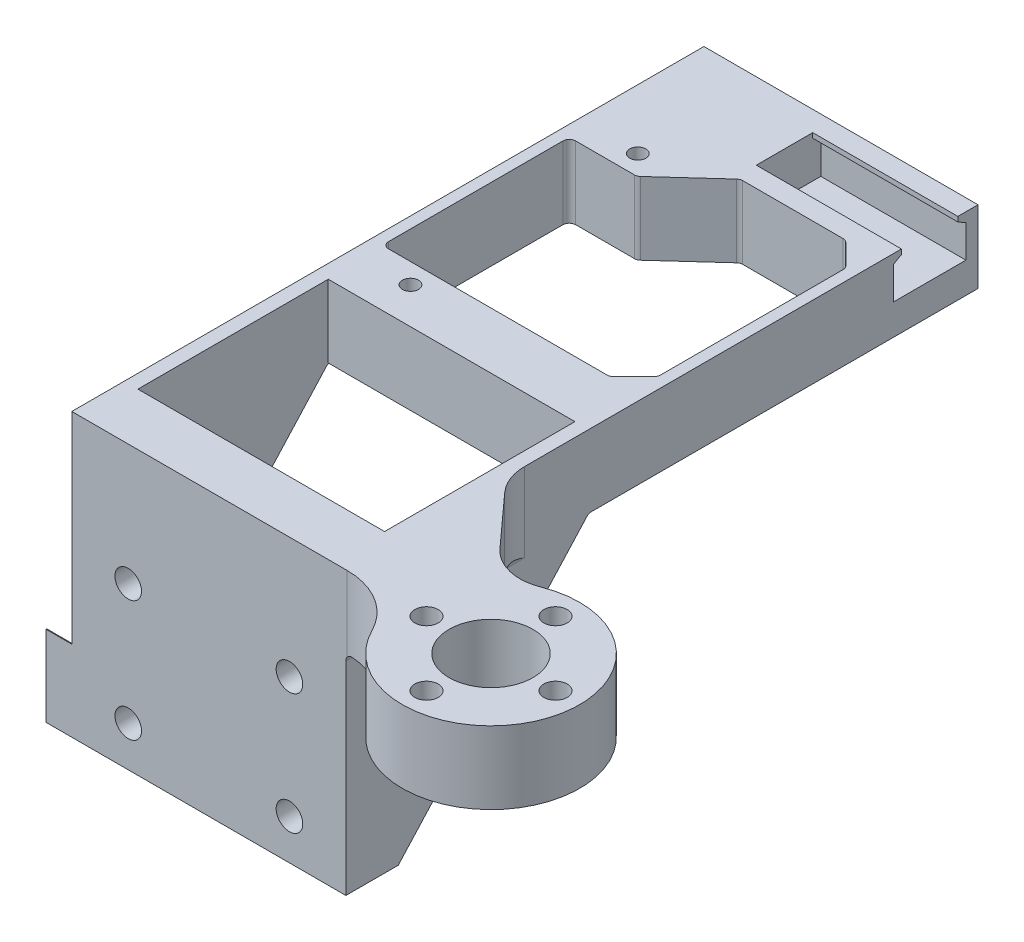
SolidWorks part; units mm, degrees
ref_plane "Front Plane" through (0, 0, 0) normal (0, 0, 1) x (1, 0, 0)
ref_plane "Top Plane" through (0, 0, 0) normal (0, 1, 0) x (1, 0, 0)
ref_plane "Right Plane" through (0, 0, 0) normal (1, 0, 0) x (0, 0, -1)
sketch "Sketch1" plane through (0, 0, 0) normal (0, 1, 0) x (1, 0, 0)
  line L0 (0, 0) -> (0, 59.6401) construction
  line L1 (-20, -19.2885) -> (-21.4, -19.2885)
  line L2 (20, 17.7115) -> (21.4, 17.7115)
  line L3 (20, 17.7115) -> (20, 69.9115)
  line L4 (20, 69.9115) -> (21.4, 69.9115)
  line L5 (21.4, 17.7115) -> (21.4, 69.9115)
  line L6 (20, 17.7115) -> (21.4, 17.7115)
  line L7 (20, 17.7115) -> (20, -19.2885)
  line L8 (20, -19.2885) -> (21.4, -19.2885)
  line L9 (21.4, 17.7115) -> (21.4, -19.2885)
  line L10 (-21.4, 17.7115) -> (-21.4, -19.2885)
  line L11 (-20, 17.7115) -> (-21.4, 17.7115)
  line L12 (-20, 17.7115) -> (-20, -19.2885)
  line L13 (-20, 69.9115) -> (-21.4, 69.9115)
  line L14 (-21.4, 17.7115) -> (-21.4, 69.9115)
  line L15 (-20, 17.7115) -> (-21.4, 17.7115)
  line L16 (-20, 17.7115) -> (-20, 69.9115)
  dimension "18" = 20
  dimension "D2" = 1.4
  dimension "D3" = 37
  dimension "D4" = 52.2
extrude "Boss-Extrude1" add sketch "Sketch1" against normal blind 9 from offset 1 contours L12 L11 L10 L1 | L11 L16 L13 L14 | L3 L2 L5 L4 offset against normal yes
sketch "Sketch4" plane through (0, -10, 0) normal (0, -1, 0) x (1, 0, 0)
  line L0 (-21.4, -69.9115) -> (-21.4, 19.2885) construction
  line L1 (12, -69.9115) -> (-21.4, -69.9115)
  line L2 (12, -69.9115) -> (12, -57.9115)
  line L3 (12, -57.9115) -> (-21.4, -57.9115)
  line L4 (-21.4, -69.9115) -> (-21.4, -57.9115)
  line L10 (-20, -69.9115) -> (-20, 19.2885) construction
  line L13 (-20, -69.9115) -> (-21.4, -69.9115) construction
  dimension "D1" = 12
  dimension "D2" = 32
extrude "Boss-Extrude3" add sketch "Sketch4" against normal up to surface (9 mm away) up to face at (-20.7, -1, -25.3115)
sketch "Sketch3" plane through (0, -10, 0) normal (0, -1, 0) x (1, 0, 0)
  line L0 (-21.4, -69.9115) -> (-21.4, 19.2885) construction
  line L1 (-21.4, -58.8115) -> (-7.4, -58.8115)
  line L2 (-21.4, -58.8115) -> (-21.4, -51.8115)
  line L3 (-21.4, -51.8115) -> (-7.4, -51.8115)
  line L4 (-7.4, -58.8115) -> (-7.4, -51.8115)
  line L6 (0, 0) -> (0, -31.4212) construction
  line L13 (12, -69.9115) -> (-21.4, -69.9115) construction
  line L14 (-21.4, -40.2115) -> (-3.8096, -40.2115) construction
  line L15 (-21.4, -28.6115) -> (-7.4, -28.6115)
  line L16 (-7.4, -21.6115) -> (-7.4, -28.6115)
  line L17 (-21.4, -21.6115) -> (-7.4, -21.6115)
  line L18 (-21.4, -21.6115) -> (-21.4, -28.6115)
  line L19 (-20, -57.9115) -> (-20, 19.2885) construction
  circle A0 centre (-14, -54.3115) radius 1
  circle A2 centre (-14, -26.1115) radius 1
  dimension "D4" = 2.5
  dimension "D5" = 2
  dimension "D1" = 14.1
  dimension "D2" = 15.6
  dimension "D3" = 7
  dimension "D6" = 6
  dimension "D7" = 14
extrude "Servo Holder" add sketch "Sketch3" along normal blind 1 and the other way offset from surface (9 mm away) 1 other way up to plane "Top Plane"
sketch "Sketch37" plane through (0, -1, 0) normal (0, 1, 0) x (1, 0, 0)
  line L0 (-7.4, 21.6115) -> (-20, 21.6115) construction
  line L1 (12.6, 21.6115) -> (-7.4, 21.6115)
  line L2 (12.6, 21.6115) -> (12.6, 28.6115)
  line L3 (12.6, 28.6115) -> (-7.4, 28.6115)
  line L4 (-7.4, 21.6115) -> (-7.4, 28.6115)
  line L5 (-21.4, 69.9115) -> (-21.4, -19.2885) construction
  dimension "D1" = 34
extrude "Boss-Extrude19" add sketch "Sketch37" against normal up to surface (10 mm away) up to face at (-14.4, -11, -25.1115)
sketch "Sketch29" plane through (0, 0, -69.9115) normal (0, 0, -1) x (-1, 0, 0)
  line L1 (21.4, -10) -> (-12.7099, -10)
  line L2 (21.4, -10) -> (21.4, -16.1774)
  line L3 (21.4, -16.1774) -> (-12.7099, -16.1774)
  line L4 (-12.7099, -10) -> (-12.7099, -16.1774)
extrude "Cut-Extrude10" cut sketch "Sketch29" against normal through all both and the other way through all
sketch "Sketch30" plane through (0, 0, 0) normal (0, 0, 1) x (1, 0, 0)
  line L0 (-4.4, -1) -> (-4.4, -36) construction
  line L1 (12.6, -1) -> (-21.4, -1)
  line L2 (12.6, -1) -> (12.6, -36)
  line L3 (12.6, -36) -> (-21.4, -36)
  line L4 (-21.4, -1) -> (-21.4, -36)
  line L7 (-21.4, -1) -> (12.6, -1) construction
  line L9 (12.6, -1) -> (-20, -1) construction
  line L11 (-21.4, -10) -> (-21.4, -1) construction
  circle A0 centre (5.6, -31) radius 1.65
  circle A1 centre (5.6, -16) radius 1.65
  circle A2 centre (-14.4, -31) radius 1.65
  circle A3 centre (-14.4, -16) radius 1.65
  dimension "D2" = 10
  dimension "D4" = 15
  dimension "D7" = 3.3
  dimension "D8" = 3.3
  dimension "D1" = 17
  dimension "D3" = 35
  dimension "D5" = 15
  dimension "D6" = 10
extrude "Carriage Interface" add sketch "Sketch30" along normal blind 6.5 from offset 2 separate body
sketch "Sketch41" plane through (-20, 0, 0) normal (1, 0, 0) x (0, 0, -1)
  line L0 (21.6115, -1) -> (-19.2885, -1) construction
  line L1 (-2, -1) -> (-19.2885, -1)
  line L2 (-2, -1) -> (-2, -10)
  line L3 (-2, -10) -> (-19.2885, -10)
  line L4 (-19.2885, -1) -> (-19.2885, -10)
  line L5 (-2, -1) -> (-2, -36) construction
extrude "Cut-Extrude14" cut sketch "Sketch41" against normal blind 15
sketch "Sketch32" plane through (0, -36, 0) normal (0, -1, 0) x (1, 0, 0)
  line L0 (-21.4, 8.5) -> (12.6, 8.5) construction
  line L1 (30.6, 8.5) -> (19.6, 8.5) construction
  line L2 (30.6, 8.5) -> (12.6, 8.5) construction
  line L4 (-21.4, 8.5) -> (12.6, 8.5) construction
  circle A0 centre (30.6, 8.5) radius 5.2
  circle A1 centre (30.6, 8.5) radius 11
  circle A2 centre (22.6, 8.5) radius 1.45
  circle A3 centre (30.6, 16.5) radius 1.45
  circle A4 centre (38.6, 8.5) radius 1.45
  circle A5 centre (30.6, 0.5) radius 1.45
  point P4 (-4.4, 8.5)
  point P18 (30.6, 8.5)
  line M1 (-21.4, 2) -> (12.6, 2)
  line M2 (12.6, 2) -> (12.6, 8.5)
  line M3 (12.6, 8.5) -> (-21.4, 8.5)
  dimension "D1" = 8
  dimension "D2" = 22
  dimension "D4" = 10.4
  dimension "D5" = 35
  dimension "D3" = 4
extrude "Boss-Extrude14" add sketch "Sketch32" along normal blind 9 from surface at -35 contours A1 A5 A4 A3 A2 A0 M1 M3 M2 starting at face at (-3.7, -1, 5.25)
sketch "Sketch34" plane through (-21.4, 0, 0) normal (-1, 0, 0) x (0, 0, 1)
  line L1 (-21.6115, -1) -> (-21.6115, -10)
  line L5 (-69.9115, -1) -> (2, -1) construction
  line L6 (-69.9115, -10) -> (2, -10) construction
  line L7 (-21.6115, -10) -> (2, -36)
  line L8 (-21.6115, -10) -> (-21.6115, -1) construction
  line L9 (2, -36) -> (8.5, -36)
  line L10 (8.5, -36) -> (8.5, -1)
  line L11 (8.5, -1) -> (-21.6115, -1)
extrude "Boss-Extrude16" add sketch "Sketch34" against normal blind 1.7
sketch "Sketch35" plane through (12.6, 0, 0) normal (1, 0, 0) x (0, 0, -1)
  line L0 (-2, -1) -> (21.6115, -1)
  line L1 (21.6115, -1) -> (21.6115, -10)
  line L3 (-8.5, -9.8) -> (-8.5, -1)
  line L4 (-8.5, -1) -> (-2, -1)
  line L5 (21.6115, -10) -> (21.6115, -1) construction
  line L6 (28.6115, -10) -> (21.6115, -10) construction
  line L8 (-8.5, -36) -> (-8.5, -1) construction
  line L9 (21.6115, -1) -> (28.6115, -1) construction
  line L10 (21.6115, -10) -> (-2, -36)
  line L11 (-2, -36) -> (-8.5, -36)
  line L12 (-8.5, -36) -> (-8.5, -9.8)
extrude "Boss-Extrude17" add sketch "Sketch35" against normal blind 1.7
sketch "Sketch36" plane through (0, -10, 0) normal (0, -1, 0) x (1, 0, 0)
  line L0 (12.6, -11.3656) -> (23.214, 0.3485)
  line L1 (12.6, 8.5) -> (20.7301, 8.5)
  line L2 (23.214, 0.3485) -> (12.6, -0.1224)
  line L3 (12.6, -0.1224) -> (12.6, -11.3656)
  line L4 (30.6, 8.5) -> (12.6, -11.3656) construction
  line L5 (12.6, 8.5) -> (12.6, 2) construction
  line L6 (20.7301, 8.5) -> (23.214, 0.3485)
  line L7 (12.6, 8.5) -> (12.6, -0.1224)
  circle A1 centre (30.6, 8.5) radius 11 construction
extrude "Boss-Extrude18" add sketch "Sketch36" against normal up to surface (9 mm away) contours L1 L7 L2 L6 | L2 L3 L0
fillet "Fillet9" [suppressed] radius 1
sketch "Sketch39" plane through (0, -1, 0) normal (0, 1, 0) x (1, 0, 0)
  line L0 (-21.4, 69.9115) -> (12, 69.9115) construction
  line L1 (12.6, 28.6115) -> (11.2, 28.6115)
  line L2 (12.6, 28.6115) -> (12.6, 69.9115)
  line L3 (12.6, 69.9115) -> (11.2, 69.9115)
  line L4 (11.2, 28.6115) -> (11.2, 69.9115)
  line L5 (-20, 28.6115) -> (12.6, 28.6115) construction
  line L6 (12.6, 11.3656) -> (12.6, 28.6115) construction
  point P7 (12.6, 49.2615)
  dimension "D1" = 1.4
extrude "Boss-Extrude20" add sketch "Sketch39" against normal up to surface (9 mm away) up to face at (-4.7667, -10, -41.9115)
sketch "Sketch40" plane through (12.6, 0, 0) normal (1, 0, 0) x (0, 0, -1)
  line L1 (60.4115, -1) -> (67.4115, -1)
  line L6 (60.4115, -2.2) -> (59.4115, -2.2)
  line L7 (59.4115, -2.2) -> (59.4115, -6.2)
  line L8 (59.4115, -6.2) -> (68.4115, -6.2)
  line L9 (63.9115, -6.2) -> (63.9115, -1)
  line L11 (68.4115, -2.2) -> (68.4115, -6.2)
  line L12 (67.4115, -2.2) -> (68.4115, -2.2)
  line L13 (67.4115, -1) -> (67.4115, -2.2)
  line L14 (69.9115, -10) -> (69.9115, -1) construction
  line L15 (60.4115, -2.2) -> (60.4115, -1)
  line L16 (11.3656, -1) -> (69.9115, -1) construction
  point P9 (59.4115, -4.2)
  dimension "D1" = 6
  dimension "D2" = 3.5
  dimension "D3" = 4.5
  dimension "D4" = 4
  dimension "D5" = 1.2
  dimension "D6" = 3.5
  dimension "D7" = 1
extrude "Brush" cut sketch "Sketch40" against normal blind 18
chamfer "Chamfer2" distance 0.6 angle 60 2 edges at (3.6, -2.2, -67.4115) (3.6, -2.2, -60.4115)
chamfer "Chamfer3" distance 3 angle 45 2 edges at (11.2, -5.5, -28.6115) (11.2, -5.5, -57.9115)
fillet "Fillet10" radius 6 2 edges at (23.214, -5.5, 0.3485) (12.6, -5.5, -11.3656)
sketch "Sketch42" plane through (0, 0, 8.5) normal (0, 0, 1) x (1, 0, 0)
  line L0 (-4.4, -36) -> (-4.4, -1) construction
  line L3 (-21.4, -36) -> (12.6, -36) construction
  line L4 (19.6, -1) -> (-21.4, -1) construction
  line L5 (-0.8, -1) -> (-0.8, -10.6)
  line L6 (-8, -1) -> (-8, -10.6)
  line L7 (-0.8, -1) -> (-8, -1)
  arc A0 (-0.8, -10.6) -> (-8, -10.6) centre (-4.4, -10.6) cw
  point P11 (-4.4, -14.2)
  dimension "D1" = 3.6
  dimension "D2" = 13.2
extrude "Cut-Extrude15" [suppressed] cut sketch "Sketch42" against normal blind 10
chamfer "Chamfer4" distance 2.5 angle 45 1 edges at (-7.4, -5.5, -57.9115)
sketch "Sketch43" plane through (0, -1, 0) normal (0, 1, 0) x (1, 0, 0)
  line L0 (-4.9, 57.9115) -> (-11.6, 51.8115)
  line L1 (-7.4, 51.8115) -> (-20, 51.8115) construction
  line L2 (-11.6, 51.8115) -> (-4.9, 51.8115)
  line L3 (-4.9, 51.8115) -> (-4.9, 57.9115)
extrude "Cut-Extrude16" cut sketch "Sketch43" against normal blind 10
fillet "Fillet11" radius 0.8 11 edges at (-20, -5.5, -51.8115) (-20, -5.5, -28.6115) (8.2, -5.5, -28.6115) (11.2, -5.5, -31.6115) (11.2, -5.5, -54.9115) (8.2, -5.5, -57.9115) (-4.9, -5.5, -57.9115) (-11.6, -5.5, -51.8115) (12.6, -10, -2.5898) (-20.55, -10, -21.6115) (11.75, -10, -21.6115)
fillet "Fillet12" radius 9 1 edges at (19.6, -5.5, 8.5)
sketch "Sketch44" plane through (0, -36, 0) normal (0, -1, 0) x (1, 0, 0)
  line L0 (-21.4, 8.5) -> (-24.6, 8.5)
  line L1 (-24.6, 8.5) -> (-24.6, 1.4)
  line L2 (-24.6, 1.4) -> (-22.9, 1.4)
  line L3 (-22.9, 1.4) -> (-22.9, 6.8)
  line L4 (-22.9, 6.8) -> (-21.4, 6.8)
  line L5 (-21.4, 2) -> (-21.4, 8.5) construction
  line L6 (-22.9, 1.4) -> (-22.2, 1.9334)
  line L7 (-22.2, 1.9334) -> (-22.9, 2.4)
  line L8 (-22.9, 2.4) -> (-22.9, 1.4)
  point P3 (-22.1, 1.9334)
  line M13 (-21.4, 8.5) -> (-21.4, 2)
  dimension "D1" = 1.7
  dimension "D2" = 1.7
  dimension "D3" = 5.4
  dimension "D4" = 1.5
  dimension "D5" = 4.4
  dimension "D6" = 0.7
extrude "Boss-Extrude21" add sketch "Sketch44" against normal blind 10 contours L3 L4 L0 L1 L2 M13 | L6 L7 L3
chamfer "Chamfer5" distance 7 angle 45 1 edges at (-23.75, -26, 1.4)
chamfer "Chamfer6" distance 1.5 angle 30 1 edges at (-22.15, -36, 6.8)
fillet "Fillet13" radius 1 1 edges at (-22.15, -34.5, 6.8)
